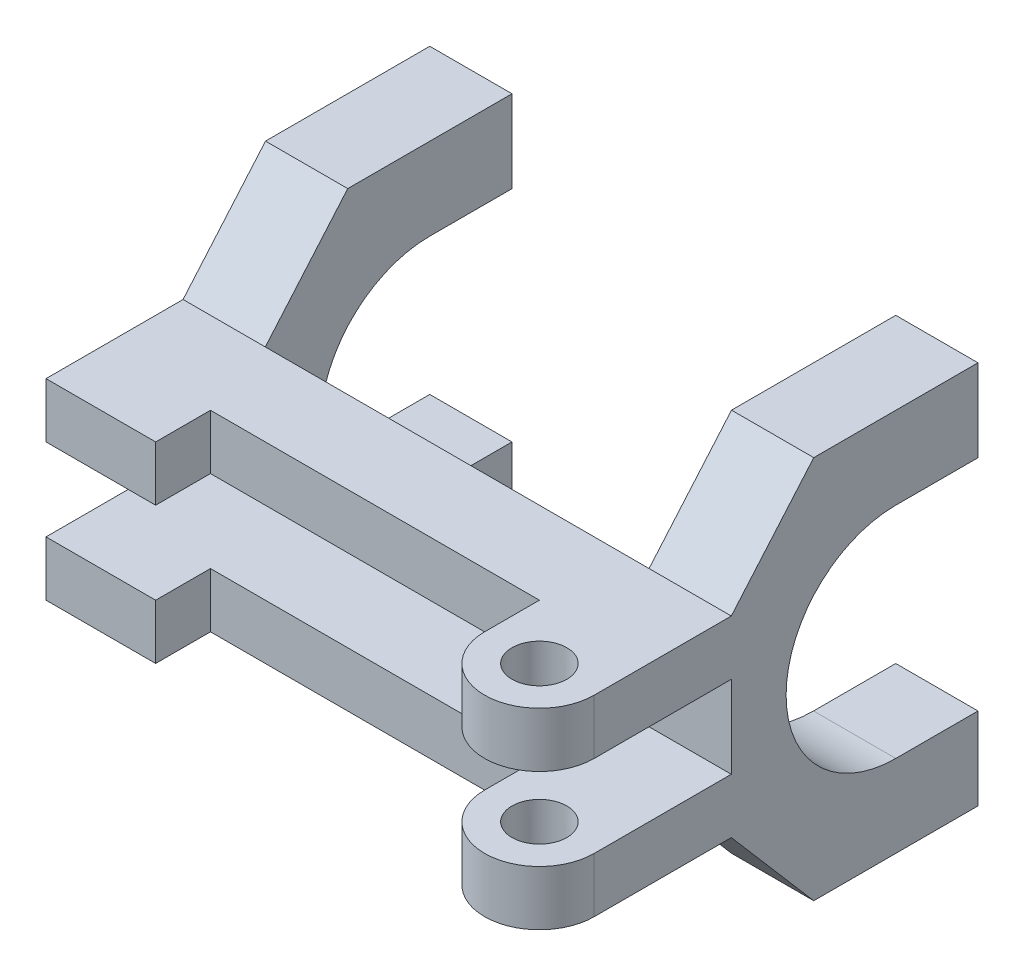
SolidWorks part; units mm, degrees
ref_plane "Front Plane" through (0, 0, 0) normal (1, 0, 0) x (0, 1, 0)
ref_plane "Top Plane" through (0, 0, 0) normal (0, 0, 1) x (0, 1, 0)
ref_plane "Right Plane" through (0, 0, 0) normal (0, 1, 0) x (-1, 0, 0)
sketch "Sketch1" plane through (0, 0, 0) normal (1, 0, 0) x (0, 1, 0)
  line L3 (0, 44.45) -> (12.7, 44.45)
  line L4 (12.7, 44.45) -> (12.7, 0)
  line L5 (12.7, 0) -> (34.925, -19.0988)
  line L6 (34.925, -19.0988) -> (34.925, -57.15)
  line L8 (0, 0) -> (-9.525, 0)
  line L9 (-9.525, 0) -> (-9.525, -12.7)
  line L10 (15.875, -38.1) -> (15.875, -57.15)
  line L11 (15.875, -57.15) -> (34.925, -57.15)
  line L12 (-9.525, -38.1) -> (-9.525, -12.7)
  line L13 (-9.525, -38.1) -> (15.875, -38.1)
  line L14 (0, 44.45) -> (0, 0)
  line L15 (12.7, 0) -> (0, 0) construction
  arc A0 (15.875, -38.1) -> (-9.525, -12.7) centre (-9.525, -38.1) ccw
  dimension "D3" = 25.4
  dimension "D1" = 44.45
  dimension "D2" = 38.0512
  dimension "D4" = 101.6
  dimension "D5" = 19.05
  dimension "D6" = 44.45
  dimension "D7" = 22.225
  dimension "D8" = 9.525
extrude "Boss-Extrude1" add sketch "Sketch1" against normal blind 127 contours A0 L10 L11 L6 L5 L4 L3 L14 L8 L9 | L15 L4 L3 L14 region at (0, 6.35, 22.225) region at (0, 18.1306, -25.6828)
sketch "Sketch2" plane through (0, 12.7, 0) normal (0, 1, 0) x (-1, 0, 0)
  line L0 (127, 31.75) -> (101.6, 31.75)
  line L1 (127, 44.45) -> (127, 0) construction
  line L2 (101.6, 31.75) -> (101.6, 19.05)
  line L3 (101.6, 19.05) -> (25.4, 19.05)
  line L4 (25.4, 19.05) -> (25.4, 31.75)
  line L5 (0, 44.45) -> (0, 0) construction
  line L6 (127, 44.45) -> (0, 44.45) construction
  arc A0 (25.4, 31.75) -> (0, 31.75) centre (12.7, 31.75) ccw
  circle A1 centre (12.7, 31.75) radius 6.35
  line M4 (0, 44.45) -> (0, 0)
  line M6 (127, 0) -> (127, 44.45)
  line M7 (127, 44.45) -> (0, 44.45)
  dimension "D5" = 12.7
  dimension "D7" = 12.7
  dimension "D1" = 25.4
  dimension "D2" = 25.4
  dimension "D3" = 12.7
  dimension "D4" = 12.7
  dimension "D6" = 12.7
extrude "Cut-Extrude1" cut sketch "Sketch2" against normal through all contours A0 L4 L3 L2 L0 M6 M7 | A0 M7 M4 | A1 region at (-2.8368, 12.7, 41.6132) region at (-70.0295, 12.7, 32.7924) region at (-12.7, 12.7, 31.75)
sketch "Sketch4" plane through (0, 34.925, 0) normal (0, 1, 0) x (-1, 0, 0)
  line L0 (19.05, -57.15) -> (19.05, 0)
  line L1 (127, -57.15) -> (0, -57.15) construction
  line L2 (19.05, 0) -> (107.95, 0)
  line L3 (107.95, 0) -> (107.95, -57.15)
  line L4 (127, 0) -> (0, 0) construction
  line L5 (0, -19.0988) -> (0, -57.15) construction
  line L6 (127, -19.0988) -> (127, -57.15) construction
  line L7 (19.05, -57.15) -> (107.95, -57.15)
  dimension "D1" = 19.05
  dimension "D2" = 19.05
extrude "Cut-Extrude2" cut sketch "Sketch4" against normal through all
mirror "Mirror1" about plane through (-127, -9.525, 0) normal (0, -1, 0) of bodies 103
